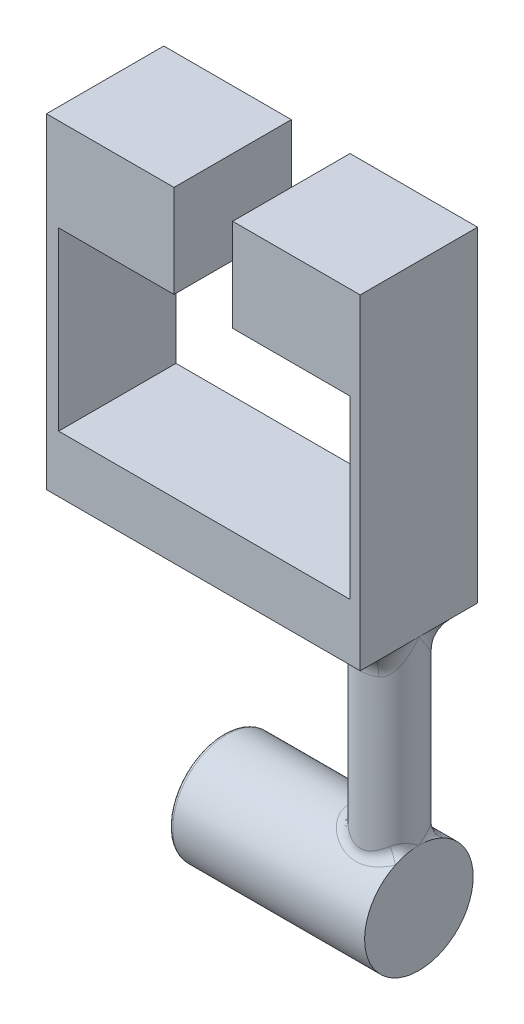
SolidWorks part; units mm, degrees
material "Plain Carbon Steel"
ref_plane "Front Plane" through (0, 0, 0) normal (0, 0, 1) x (1, 0, 0)
ref_plane "Top Plane" through (0, 0, 0) normal (0, 1, 0) x (1, 0, 0)
ref_plane "Right Plane" through (0, 0, 0) normal (1, 0, 0) x (0, 0, -1)
sketch "Sketch1" plane through (0, 0, 0) normal (0, 0, 1) x (1, 0, 0)
  line L0 (0, 0) -> (63.0428, 0)
  line L1 (63.0428, 0) -> (63.0428, 38.1)
  line L2 (63.0428, 38.1) -> (37.6631, 38.1)
  line L3 (37.6631, 38.1) -> (37.6631, 88.9)
  line L4 (37.6631, 88.9) -> (24.9631, 88.9)
  line L5 (24.9631, 88.9) -> (24.9631, 38.1)
  line L6 (24.9631, 38.1) -> (0, 38.1)
  line L7 (0, 38.1) -> (0, 0)
  line L8 (0, 38.1) -> (0, 58.166)
  line L9 (0, 58.166) -> (24.9631, 58.166)
  line L10 (0, 58.166) -> (-2.6416, 58.166)
  line L11 (-2.6416, 58.166) -> (-2.6416, -12.2936)
  line L12 (31.3131, 88.9) -> (31.3131, -8.8193) construction
  line L13 (-2.6416, -12.2936) -> (65.2678, -12.2936)
  line L14 (62.6262, 58.166) -> (37.6631, 58.166)
  line L15 (62.6262, 58.166) -> (65.2678, 58.166)
  line L16 (65.2678, 58.166) -> (65.2678, -12.2936)
  line L17 (37.6631, 58.166) -> (24.9631, 58.166)
  point P19 (31.3131, -12.2936)
  point P20 (31.3131, 88.9)
  dimension "D1" = 63.0428
  dimension "D2" = 38.1
  dimension "D3" = 25.3797
  dimension "D4" = 50.8
  dimension "D5" = 12.7
  dimension "D6" = 12.2936
  dimension "D7" = 20.066
  dimension "D8" = 2.6416
extrude "Boss-Extrude1" add sketch "Sketch1" along normal blind 25.4 contours L10 L11 L13 L16 L15 L14 L17 L9
extrude "Cut-Extrude1" cut sketch "Sketch1<4>" along normal blind 25.4 contours L7 L0 L1 L2 L3 L4 L5 L6
sketch "Sketch1<4>" plane through (0, 0, 0) normal (0, 0, 1) x (1, 0, 0) same geometry as "Sketch1"
sketch "Sketch4" plane through (0, -12.2936, 0) normal (0, -1, 0) x (1, 0, 0)
  line L0 (62.6262, 0) -> (37.6631, 0) construction
  line L1 (65.2678, 25.4) -> (65.2678, 0) construction
  circle A0 centre (58.9178, 12.7) radius 6.35
  dimension "D1" = 12.7
  dimension "D2" = 12.7
extrude "Boss-Extrude2" add sketch "Sketch4" along normal blind 50.8
sketch "Sketch5" plane through (65.2678, 0, 0) normal (1, 0, 0) x (0, 0, -1)
  line L0 (-19.05, -63.0936) -> (-6.35, -63.0936) construction
  circle A0 centre (-12.7, -63.0936) radius 11.7475
  dimension "D1" = 23.495
extrude "Boss-Extrude3" add sketch "Sketch5" against normal blind 42.291
fillet "Fillet1" radius 6.35 1 edges at (65.2678, -12.2936, 12.7)
fillet "Fillet2" radius 2.54 1 edges at (52.5678, -51.3461, 12.7)
fillet "Fillet3" radius 0.762 1 edges at (22.9768, -63.0936, 0.9525)
equation "\"D-Pin\"= .925"
equation "\"D-PinMount\"= .50"
equation "\"Bottom Plate Thickness\"= .484"
equation "\"Vertical colomn Thickness\" = .104"
equation "\"Top Flange Thickness\"= .79"
equation "\"D6@Sketch1\"=\"Bottom Plate Thickness\""
equation "\"D7@Sketch1\"=\"Top Flange Thickness\""
equation "\"D8@Sketch1\"=\"Vertical colomn Thickness\""
equation "\"D1@Sketch4\"=\"D-PinMount\""
equation "\"Part Thickness\"= 1"
equation "\"D2@Sketch4\"=\"Part Thickness\"/2"
equation "\"D1@Boss-Extrude1\"=\"Part Thickness\""
equation "\"D1@Sketch5\"=\"D-Pin\""
equation "\"D3@Sketch1\"=.9992"
